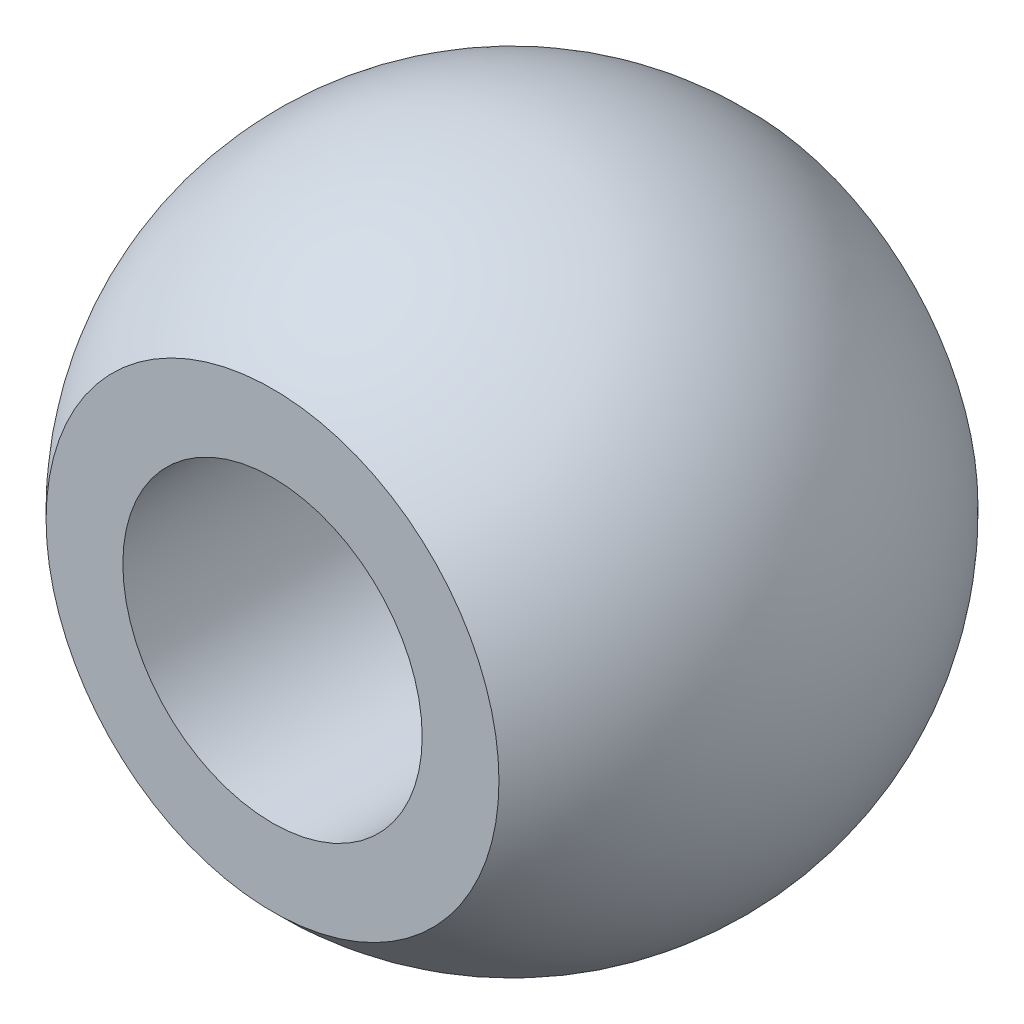
SolidWorks part; units mm, degrees
ref_plane "Front Plane" through (0, 0, 0) normal (0, 0, 1) x (1, 0, 0)
ref_plane "Top Plane" through (0, 0, 0) normal (0, 1, 0) x (1, 0, 0)
ref_plane "Right Plane" through (0, 0, 0) normal (1, 0, 0) x (0, 0, -1)
sketch "Sketch1" plane through (0, 0, 0) normal (0, 0, 1) x (1, 0, 0)
  line L0 (0, -1000) -> (0, 49000) construction
  circle A0 centre (0, 0) radius 5.505
  dimension "D1" = 11.01
revolve "Revolve2" add sketch "Sketch1" angle 360 about L0 region at (2.3364, 0, 0)
sketch "Sketch2" plane through (0, 0, 0) normal (0, 0, 1) x (1, 0, 0)
  circle A0 centre (0, 0) radius 2.5
  dimension "D1" = 5
extrude "Cut-Extrude1" cut sketch "Sketch2" against normal through all both and the other way through all
ref_plane "Plane1" through (0, 0, 4) normal (0, 0, 1) x (1, 0, 0)
sketch "Sketch3" plane through (0, 0, 4) normal (0, 0, 1) x (1, 0, 0)
  line L1 (-8.1307, -8.0918) -> (8.1307, -8.0918)
  line L2 (-8.1307, -8.0918) -> (-8.1307, 8.0918)
  line L3 (-8.1307, 8.0918) -> (8.1307, 8.0918)
  line L4 (8.1307, -8.0918) -> (8.1307, 8.0918)
  line L5 (-8.1307, -8.0918) -> (8.1307, 8.0918) construction
  line L6 (-8.1307, 8.0918) -> (8.1307, -8.0918) construction
  point P0 (0, 0)
extrude "Cut-Extrude2" cut sketch "Sketch3" along normal through all
mirror "Mirror1" about plane through (0, 0, 0) normal (0, 0, 1) of "Cut-Extrude2"
ref_axis "Axis1" through (0, 0, -4.4) along (0, 0, 1)
